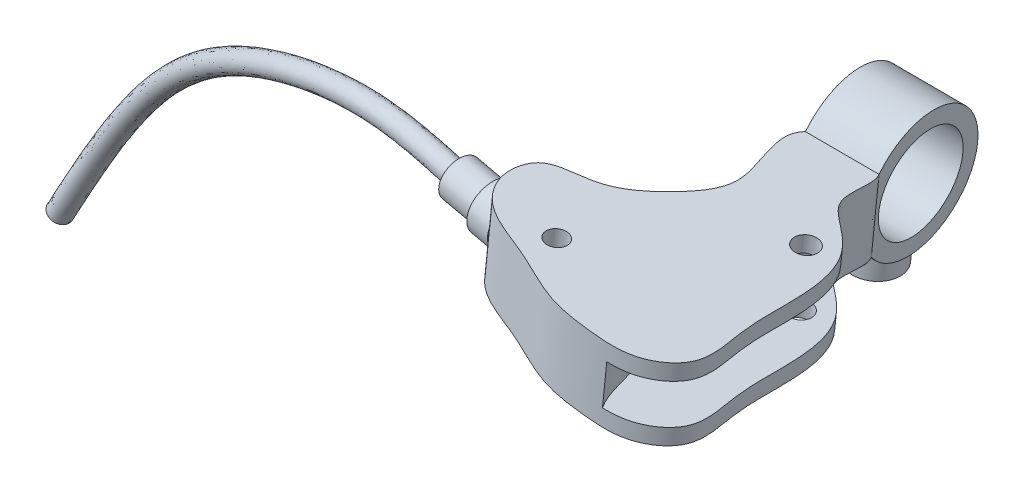
SolidWorks part; units mm, degrees
material "Aleación 6061"
ref_plane "Alzado" through (0, 0, 0) normal (0, 0, 1) x (1, 0, 0)
ref_plane "Planta" through (0, 0, 0) normal (0, 1, 0) x (1, 0, 0)
ref_plane "Vista lateral" through (0, 0, 0) normal (1, 0, 0) x (0, 0, -1)
sketch3d "Sk_Abrazadera"
  line L0 (231.9631, 41.8477, -24.5933) -> (247.8038, 40.2316, -26.1614)
  dimension "D1" = 16
sweep "Abrazadera" add path "Sk_Abrazadera" circular profile diameter 30 parameters "D3"=30
sketch3d "Sk_Orejeta_tornillo"
  line L0 (238.8685, 31.0913, -25.3774) -> (237.7521, 20.1481, -25.3774)
  dimension "D1" = 11
sweep "Orejeta_tornillo" add path "Sk_Orejeta_tornillo" circular profile diameter 12 parameters "D3"=12
sketch3d "Sk_puntos_Plano_maneta"
  point P0 (247.8038, 40.2316, -26.1614)
  point P1 (297.3062, 35.1814, -31.0616)
  point P2 (252.6788, 39.7343, 23.5979)
ref_plane "Plano_maneta" through (6.6148, 64.8378, 0) normal (-0.1015, -0.9948, 0) x (-0.9948, 0.1015, 0)
sketch "Sk_Cuerpo" plane through (6.6148, 64.8378, 0) normal (-0.1015, -0.9948, 0) x (-0.9948, 0.1015, 0)
  spline S0 degree 3 poles (-247.7512, 19.043) (-219.2378, 14.8287) (-233.0703, -3.9125) (-224.3795, -16.5455) (-215.9984, -24.7968) (-204.0634, -25.3721) (-202.2986, -34.6945) (-207.5963, -43.1878) (-219.6304, -45.8033) (-230.7037, -51.8113) (-242.0526, -52.3892) (-251.9269, -52.068) (-260.8099, -44.2141) (-257.2989, -31.2772) (-258.4685, -18.7548) (-256.3278, -6.3369) (-249.6245, -0.5608) (-242.3483, 4.3803) (-247.7512, 19.043) (-219.2378, 14.8287) (-233.0703, -3.9125) knots -0.159656 -0.128106 -0.078835 0 0.088689 0.146149 0.210392 0.261833 0.292995 0.330519 0.398969 0.465074 0.515322 0.564655 0.608518 0.667849 0.74192 0.801862 0.840344 0.871894 0.921165 1 1.088689 1.146149 1.210392 only from (-227.6941, 12.6511) to (-227.6941, 12.6511)
extrude "Cuerpo" add sketch "Sk_Cuerpo" along normal mid plane 18
sketch3d "Sk_Contratuerca"
  line L0 (211.6817, 43.9168, 33.8823) -> (206.237, 44.4723, 33.3374)
  dimension "D1" = 5.5
sweep "Contratuerca" add path "Sk_Contratuerca" circular profile diameter 11.5 parameters "D3"=11.5
sketch3d "Sk_Regulador_cable"
  line L0 (206.237, 44.4723, 33.3374) -> (197.3275, 45.3812, 32.4458)
  dimension "D1" = 9
sweep "Regulador_cable" add path "Sk_Regulador_cable" circular profile diameter 9 parameters "D3"=9
sketch3d "Sk_Funda_cable"
  spline S0 degree 3 poles (198.3175, 45.2802, 32.5448) (191.4116, 46.327, 31.8139) (173.7972, 48.997, 29.9494) (141.0079, 41.8099, 27.8947) (109.7438, 15.0723, 18.9485) (95.1692, -10.7432, 17.8995) (87.7659, -23.8565, 17.3666) knots 0 0 0 0 0.147729 0.376804 0.683439 1 1 1 1
sweep "Funda_cable" add path "Sk_Funda_cable" circular profile diameter 5 parameters "D3"=5
sketch "Sk_Ranura_palanca" plane through (6.6148, 64.8378, 0) normal (-0.1015, -0.9948, 0) x (-0.9948, 0.1015, 0)
  spline S0 degree 3 poles (-232.2258, -11.9649) (-237.8557, 2.2413) (-250.578, 5.8543) (-267.486, 1.6073) (-260.9854, -24.5451) (-278.9085, -54.2558) (-243.0351, -59.4222) (-243.6976, -37.6813) (-232.7822, -26.7229) (-232.2258, -11.9649) (-237.8557, 2.2413) (-250.578, 5.8543) knots -0.266705 -0.195409 -0.106133 0 0.065032 0.133713 0.287289 0.485075 0.606236 0.733295 0.804591 0.893867 1 1.065032 1.133713 1.287289 only from (-240.8124, 1.8849) to (-240.8124, 1.8849)
extrude "Ranura_palanca" cut sketch "Sk_Ranura_palanca" against normal mid plane 10
sketch3d "Sk_Agujero_pivote"
  line L0 (253.0675, 27.6323, 8.3663) -> (255.5034, 51.5084, 8.3663)
  dimension "D1" = 24
sweep "Agujero_pivote" cut path "Sk_Agujero_pivote" circular profile diameter 5.5 parameters "D3"=5.5
sketch3d "Sk_Agujero_abrazadera"
  line L0 (230.973, 41.9487, -24.4953) -> (248.7939, 40.1306, -26.2594)
  dimension "D1" = 18
sweep "Agujero_abrazadera" cut path "Sk_Agujero_abrazadera" circular profile diameter 22.2 parameters "D3"=22.2
sketch3d "Sk_Agujero_tornillo_M5"
  line L0 (237.3821, 25.2118, -34.334) -> (239.1371, 25.0328, -16.4207)
  dimension "D1" = 18
sweep "Agujero_tornillo_M5" cut path "Sk_Agujero_tornillo_M5" circular profile diameter 5.5 parameters "D3"=5.5
sketch3d "Sk_Paso_cable_cuerpo"
  line L0 (208.7119, 44.2198, 33.5851) -> (247.241, 40.289, 19.112)
  dimension "D1" = 41.3451
sweep "Paso_cable_cuerpo" cut path "Sk_Paso_cable_cuerpo" circular profile diameter 2.5 parameters "D3"=2.5
sketch3d "Sk_Aligerado"
  line L0 (225.007, 30.4951, 39.2795) -> (227.4429, 54.3711, 39.2795)
  dimension "D1" = 24
sweep "Aligerado" cut path "Sk_Aligerado" circular profile diameter 5 parameters "D3"=5
